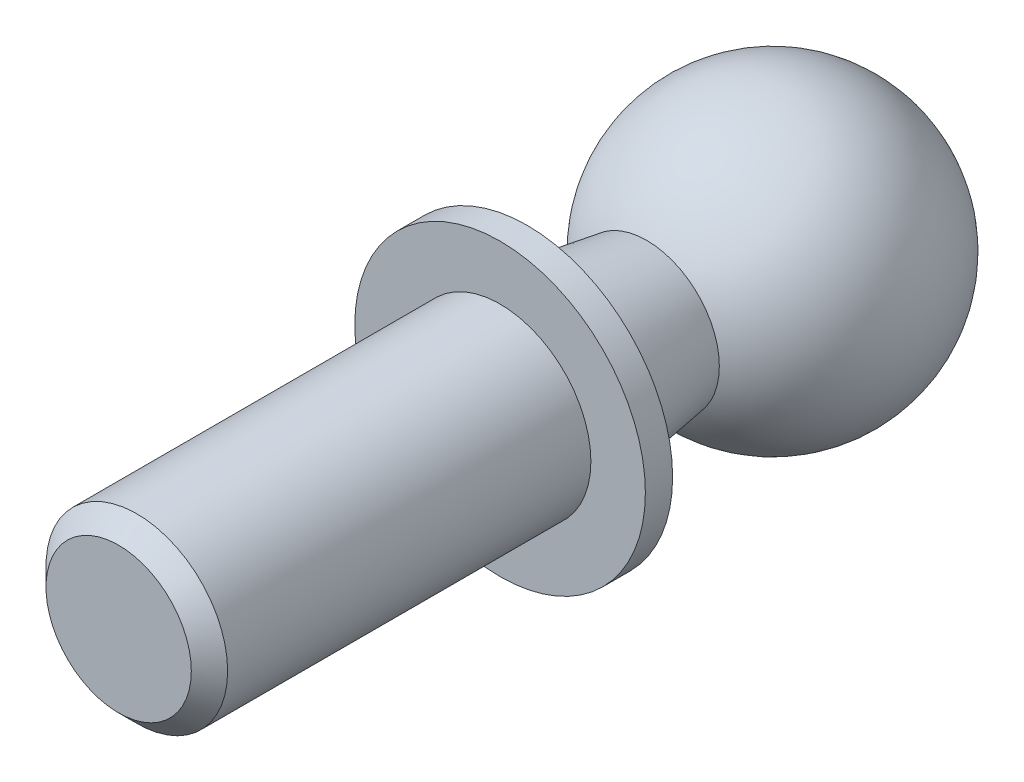
SolidWorks part; units mm, degrees
ref_plane "Front Plane" through (0, 0, 0) normal (0, 0, 1) x (1, 0, 0)
ref_plane "Top Plane" through (0, 0, 0) normal (0, 1, 0) x (1, 0, 0)
ref_plane "Right Plane" through (0, 0, 0) normal (1, 0, 0) x (0, 0, -1)
sketch "Sketch1" plane through (0, 0, 0) normal (1, 0, 0) x (0, 0, -1)
  line L0 (-16, 5) -> (-13.5, 5)
  line L1 (-13.5, 5) -> (-6.9282, 4)
  line L2 (-16, 5) -> (-16, 0) construction
  line L3 (-16, 0) -> (-16, -5) construction
  line L4 (-16, 0) -> (0, 0) construction
  line L5 (-16, 0) -> (-26, 0) construction
  line L6 (-36, -5) -> (-16, -5)
  line L7 (-36, -5) -> (-36, 5)
  line L8 (-36, 5) -> (-16, 5)
  line L9 (-16, -5) -> (-16, 5)
  line L10 (-36, -5) -> (-16, 5) construction
  line L11 (-36, 5) -> (-16, -5) construction
  line L12 (-16, -5) -> (-13.5, -5)
  line L13 (-15, -8) -> (-13.5, -8)
  line L14 (-15, -8) -> (-15, 8)
  line L15 (-15, 8) -> (-13.5, 8)
  line L16 (-13.5, -8) -> (-13.5, 8)
  line L17 (-15, -8) -> (-13.5, 8) construction
  line L18 (-15, 8) -> (-13.5, -8) construction
  line L19 (-13.5, -5) -> (-6.9282, -4)
  line L20 (-6.9282, 4) -> (-6.9282, -4) construction
  line L21 (-36, 0) -> (8, 0)
  line L22 (8, 0) -> (10.8696, 0)
  circle A0 centre (0, 0) radius 8
  point P7 (-26, 0)
  point P9 (-14.25, 0)
  dimension "D1" = 16
  dimension "D2" = 10
  dimension "D3" = 20
  dimension "D4" = 16
  dimension "D5" = 16
  dimension "D6" = 8
  dimension "D7" = 2.5
  dimension "D8" = 1.5
revolve "Revolve4" add sketch "Sketch1" angle 360 about L22 region at (0, 2.5, 26) region at (0, 2.5, 15.5) region at (0, 6.5, 14.25) region at (0, 2.5, 14.25) region at (0, 2.3402, 10.6592) region at (0, 3.3953, 0)
chamfer "Chamfer1" distance 1 angle 45 1 edges at (5, 0, 36)
ref_axis "Axis1" through (0, 0, 13.5) along (0, 0, -1)
